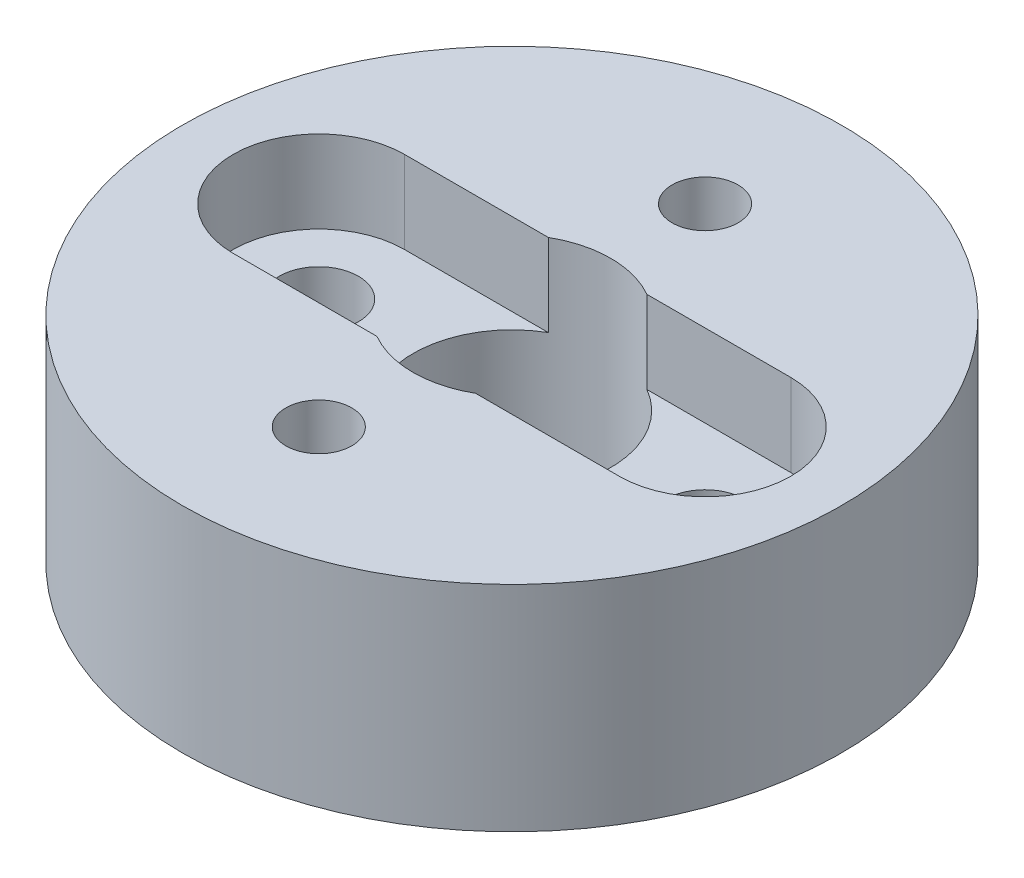
SolidWorks part; units mm, degrees
ref_plane "Front" through (0, 0, 0) normal (0, 0, 1) x (1, 0, 0)
ref_plane "Top" through (0, 0, 0) normal (0, 1, 0) x (1, 0, 0)
ref_plane "Right" through (0, 0, 0) normal (1, 0, 0) x (0, 0, -1)
sketch "Sketch1" plane through (0, 0, 0) normal (0, 1, 0) x (1, 0, 0)
  line L0 (0, 0) -> (7.4422, 0) construction
  line L1 (0, 0) -> (0, 2.3523) construction
  circle A1 centre (0, 0) radius 12.7
  circle A2 centre (7.4422, 0) radius 1.524
  circle A3 centre (-7.4422, 0) radius 1.524
  dimension "D2" = 25.4
  dimension "D3" = 3.048
  dimension "D1" = 7.4422
extrude "Boss-Extrude1" add sketch "Sketch1" along normal blind 8.255
sketch "Sketch2" plane through (0, 8.255, 0) normal (0, 1, 0) x (1, 0, 0)
  circle A0 centre (-7.4422, 0) radius 3.302
  circle A1 centre (7.4422, 0) radius 3.302
  point P6 (0, 0)
  point P7 (7.4422, 0)
  point P8 (0, 0)
  dimension "D1" = 6.604
extrude "r" cut sketch "Sketch2" against normal blind 3.175
sketch "Sketch3" plane through (0, 8.255, 0) normal (0, 1, 0) x (1, 0, 0)
  line L0 (0, 0) -> (0, -7.4422) construction
  line L1 (0, 0) -> (1.0233, 0) construction
  circle A0 centre (0, -7.4422) radius 1.27
  circle A1 centre (0, 7.4422) radius 1.27
  dimension "D1" = 7.4422
  dimension "D2" = 2.54
extrude "Cut-Extrude2" cut sketch "Sketch3" against normal through all
sketch "Sketch4" plane through (0, 8.255, 0) normal (0, 1, 0) x (1, 0, 0)
  circle A0 centre (0, 0) radius 3.81
  dimension "D1" = 7.62
extrude "Cut-Extrude3" cut sketch "Sketch4" against normal through all
sketch "Sketch5" plane through (0, 8.255, 0) normal (0, 1, 0) x (1, 0, 0)
  line L0 (-7.4422, 0) -> (7.4422, 0) construction
  line L1 (-7.4422, 3.302) -> (7.4422, 3.302)
  line L2 (-7.4422, -3.302) -> (7.4422, -3.302)
  arc A0 (-7.4422, 3.302) -> (-7.4422, -3.302) centre (-7.4422, 0) ccw
  arc A1 (7.4422, -3.302) -> (7.4422, 3.302) centre (7.4422, 0) ccw
  circle A4 centre (7.4422, 0) radius 3.302 construction
  point P3 (0, 0)
extrude "Cut-Extrude4" cut sketch "Sketch5" against normal up to surface (3.175 mm away) up to face at (-7.4422, 5.08, 1.524)
equation "\"Spacing\"= 0.293"
equation "\"D1@Sketch1\"=\"Spacing\""
equation "\"D1@Sketch3\"=\"Spacing\""
